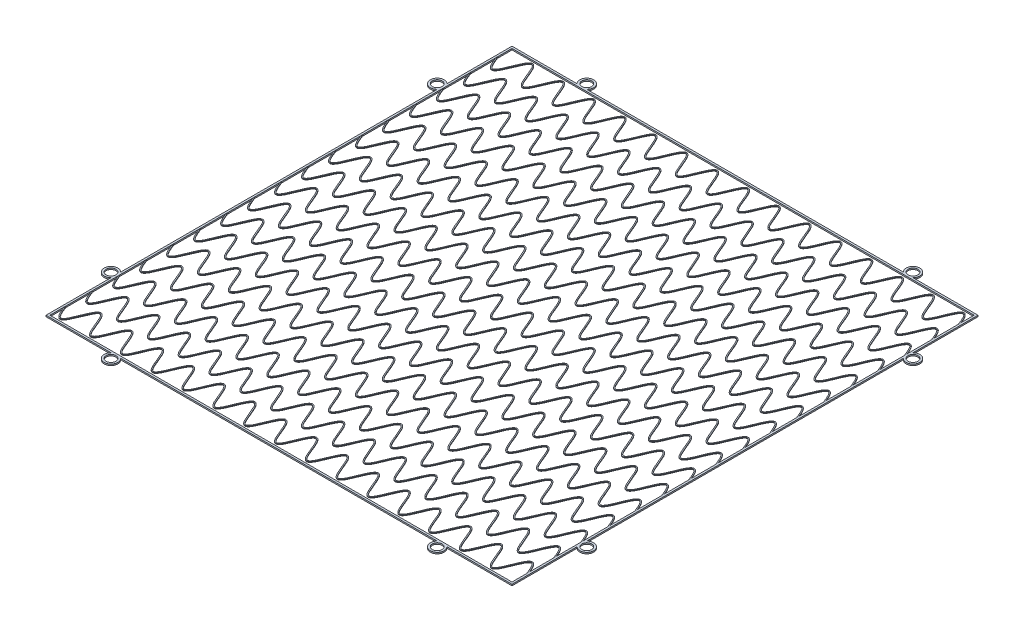
SolidWorks part; units mm, degrees
ref_plane "Front" through (0, 0, 0) normal (0, 0, 1) x (1, 0, 0)
ref_plane "Top" through (0, 0, 0) normal (0, 1, 0) x (1, 0, 0)
ref_plane "Right" through (0, 0, 0) normal (1, 0, 0) x (0, 0, -1)
ref_axis "X" through (-80.9, 0, 0) along (1, 0, 0)
ref_axis "Y" through (0, -50, 0) along (0, 1, 0)
ref_axis "Z" through (0, 0, -80.9) along (0, 0, 1)
sketch "Sketch1" plane through (0, 0, 0) normal (0, 1, 0) x (1, 0, 0)
  line L0 (-94.2, 94.2) -> (94.2, 94.2)
  line L1 (-95, 95) -> (95, 95)
  line L2 (-95, 95) -> (-95, -95)
  line L3 (-95, -95) -> (95, -95)
  line L4 (95, 95) -> (95, -95)
  line L5 (-95, 95) -> (95, -95) construction
  line L6 (-95, -95) -> (95, 95) construction
  line L7 (94.2, 94.2) -> (94.2, -94.2)
  line L8 (-94.2, -94.2) -> (94.2, -94.2)
  line L9 (-94.2, 94.2) -> (-94.2, -94.2)
  point P4 (0, 0)
  point P5 (0, 0)
  dimension "D1" = 190
  dimension "D2" = 0.8
extrude "Boss-Extrude1" add sketch "Sketch1" along normal mid plane 0.56
sketch "Sketch5" plane through (0, 0, 0) normal (0, 1, 0) x (1, 0, 0)
  line L7 (-95, 95) -> (-95, -95) construction
  line L8 (94.2, 94.2) -> (-94.2, 94.2) construction
  line L9 (95, 95) -> (-95, 95) construction
  circle A0 centre (-66.5, 97) radius 2
  circle A1 centre (-66.5, 97) radius 2.8
  point P3 (-66.5, 97.1719)
  dimension "D1" = 4
  dimension "D2" = 28.5
extrude "Boss-Extrude5" add sketch "Sketch5" along normal mid plane 0.56
mirror "Mirror2" about plane through (0, 0, 0) normal (1, 0, 0) of "Boss-Extrude5"
pattern_circular "CirPattern1" count 4 over 360 about axis through (0, -50, 0) along (0, 1, 0) of "Mirror2"
sketch "Sketch7" plane through (0, 0, 0) normal (0, 1, 0) x (1, 0, 0)
  line L0 (-94.6855, 0.5541) -> (-94.3145, 0.7037)
  line L1 (94.3145, -0.7037) -> (94.6855, -0.5541)
  spline S0 degree 4 number of poles 541 (-94.9666, 1.7589) -> (94.9853, -1.8026) construction
  spline S1 degree 4 number of poles 533 (-94.5, 0.6289) -> (94.5, -0.6289) construction
  spline S2 degree 1 poles (-94.6855, 0.5541) (94.3145, -0.7037) knots 0 0 1 1 construction
  spline S3 degree 3 number of poles 399 (-94.6855, 0.5541) -> (94.3145, -0.7037)
  spline S4 degree 1 poles (-94.3145, 0.7037) (94.6855, -0.5541) knots 0 0 1 1 construction
  spline S5 degree 3 number of poles 399 (-94.3145, 0.7037) -> (94.6855, -0.5541)
  point P0 (-242.0859, 104.7437)
  dimension "D1" = 0.2
  dimension "D2" = 0.2
extrude "Boss-Extrude7" add sketch "Sketch7" along normal mid plane 0.28
pattern_linear "LPattern6" count 9 spacing 11 along (0, 0, -1) count 9 spacing 11 along (0, 0, 1) of "Boss-Extrude7" pattern seed only yes
